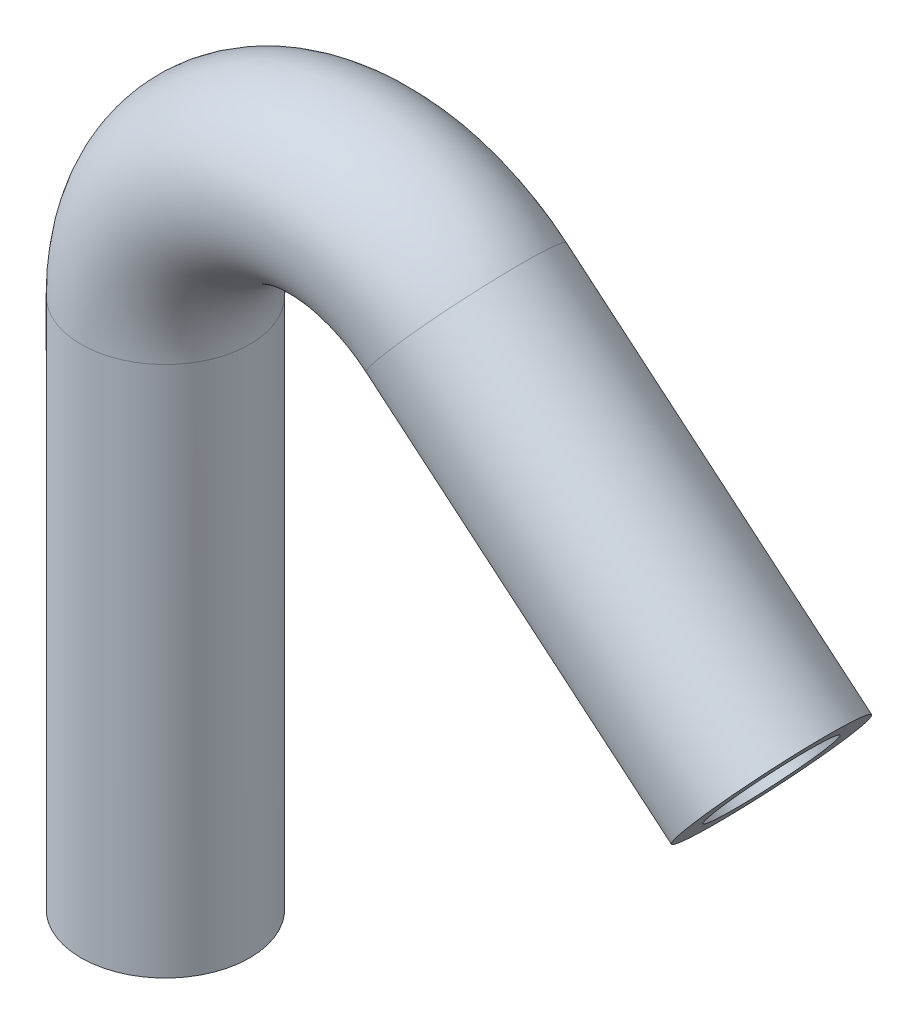
SolidWorks part; units mm, degrees
ref_plane "Piano frontale" through (0, 0, 0) normal (0, 0, 1) x (1, 0, 0)
ref_plane "Piano superiore" through (0, 0, 0) normal (0, 1, 0) x (1, 0, 0)
ref_plane "Piano destro" through (0, 0, 0) normal (1, 0, 0) x (0, 0, -1)
sketch "Schizzo1" plane through (0, 0, 0) normal (0, 0, 1) x (1, 0, 0)
  line L0 (0, 0) -> (0, 20)
  line L1 (11.3242, 25.2806) -> (22.8149, 15.6388)
  arc A0 (0, 20) -> (11.3242, 25.2806) centre (6.8933, 20) cw
  point P6 (10.2704, 25.8494)
  dimension "D1" = 15
  dimension "D2" = 20
  dimension "D3" = 50
sweep "Sweep-Sottile1" add path "Schizzo1" circular profile diameter 6.35 parameters "D1"=1, "D3"=6.35
